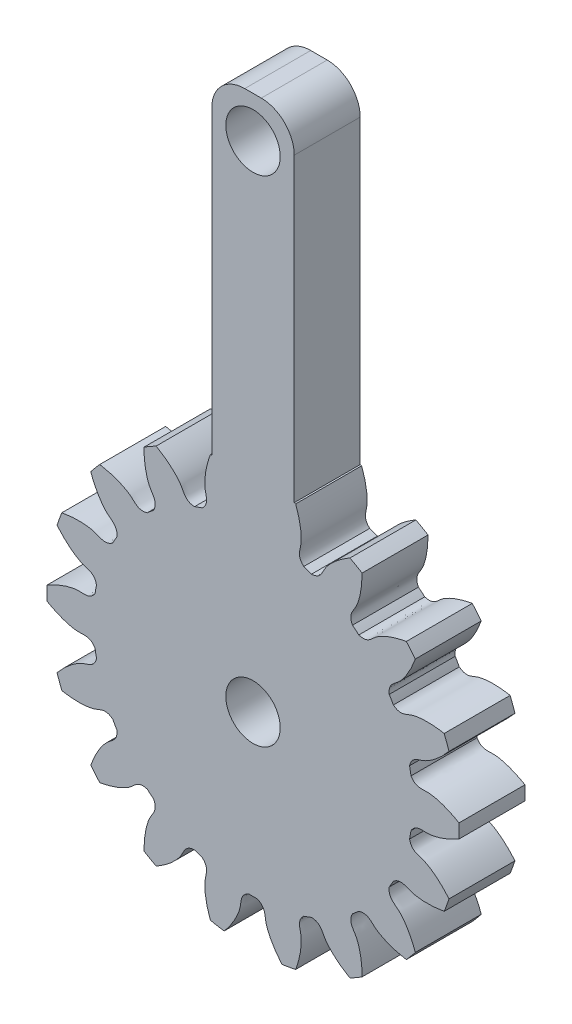
SolidWorks part; units mm, degrees
ref_plane "前视基准面" through (0, 0, 0) normal (0, 0, 1) x (1, 0, 0)
ref_plane "上视基准面" through (0, 0, 0) normal (0, 1, 0) x (1, 0, 0)
ref_plane "右视基准面" through (0, 0, 0) normal (1, 0, 0) x (0, 0, -1)
sketch "草图1" plane through (0, 0, 0) normal (0, 0, 1) x (1, 0, 0)
  circle A0 centre (0, 0) radius 12.5
extrude "凸台-拉伸1" add sketch "草图1" along normal blind 4
ref_axis "基准轴1" through (0, 0, -0.15) along (0, 0, 1)
sketch "草图2" plane through (0, 0, 0) normal (0, 0, 1) x (1, 0, 0)
  line L0 (0, 0) -> (0, 12.5) construction
  circle A0 centre (0, 0) radius 12.5 construction
  arc A1 (0.2493, 9.6843) -> (-0.2493, 9.6843) centre (0, 0) ccw
  arc A2 (3.8732, 14.1333) -> (-3.8732, 14.1333) centre (0, 0) ccw
  spline S0 degree 3 poles (0.2493, 9.6843) (0.7689, 9.8984) (0.7035, 10.2984) (0.7898, 10.6782) (0.7984, 10.7131) (0.8089, 10.7519) (0.8213, 10.7946) (0.8358, 10.841) (0.8526, 10.8911) (0.8718, 10.9449) (0.8935, 11.0022) (0.918, 11.063) (0.9453, 11.1272) (0.9757, 11.1947) (1.0092, 11.2654) (1.046, 11.3392) (1.0863, 11.416) (1.1301, 11.4956) (1.1776, 11.5781) (1.2289, 11.6632) (1.2842, 11.7508) (1.3435, 11.8408) (1.407, 11.9332) (1.4749, 12.0276) (1.5471, 12.1241) (1.6238, 12.2225) (1.7052, 12.3225) (1.7913, 12.4242) (1.8822, 12.5273) (1.978, 12.6316) (2.0788, 12.7371) (2.1846, 12.8436) (2.2956, 12.9508) (2.4118, 13.0587) (2.5334, 13.1671) (2.6602, 13.2757) (2.7925, 13.3845) (2.9303, 13.4932) (3.0735, 13.6017) (3.2224, 13.7099) (3.3768, 13.8174) (3.5926, 13.9613) (3.7594, 14.0654) (3.8732, 14.1333) knots 0 0 0 0 0.187592 0.192996 0.199121 0.205966 0.213531 0.221818 0.230824 0.240552 0.250999 0.262168 0.274057 0.286666 0.299996 0.314047 0.328818 0.344309 0.360521 0.377454 0.395107 0.413481 0.432575 0.45239 0.472926 0.494181 0.516158 0.538855 0.562272 0.58641 0.611269 0.636848 0.663148 0.690168 0.717909 0.74637 0.775552 0.805454 0.836077 0.867421 0.899485 0.932269 1 1 1 1
  spline S1 degree 3 poles (-0.2493, 9.6843) (-0.7689, 9.8984) (-0.7035, 10.2984) (-0.7898, 10.6782) (-0.7984, 10.7131) (-0.8089, 10.7519) (-0.8213, 10.7946) (-0.8358, 10.841) (-0.8526, 10.8911) (-0.8718, 10.9449) (-0.8935, 11.0022) (-0.918, 11.063) (-0.9453, 11.1272) (-0.9757, 11.1947) (-1.0092, 11.2654) (-1.046, 11.3392) (-1.0863, 11.416) (-1.1301, 11.4956) (-1.1776, 11.5781) (-1.2289, 11.6632) (-1.2842, 11.7508) (-1.3435, 11.8408) (-1.407, 11.9332) (-1.4749, 12.0276) (-1.5471, 12.1241) (-1.6238, 12.2225) (-1.7052, 12.3225) (-1.7913, 12.4242) (-1.8822, 12.5273) (-1.978, 12.6316) (-2.0788, 12.7371) (-2.1846, 12.8436) (-2.2956, 12.9508) (-2.4118, 13.0587) (-2.5334, 13.1671) (-2.6602, 13.2757) (-2.7925, 13.3845) (-2.9303, 13.4932) (-3.0735, 13.6017) (-3.2224, 13.7099) (-3.3768, 13.8174) (-3.5926, 13.9613) (-3.7594, 14.0654) (-3.8732, 14.1333) knots 0 0 0 0 0.187592 0.192996 0.199121 0.205966 0.213531 0.221818 0.230824 0.240552 0.250999 0.262168 0.274057 0.286666 0.299996 0.314047 0.328818 0.344309 0.360521 0.377454 0.395107 0.413481 0.432575 0.45239 0.472926 0.494181 0.516158 0.538855 0.562272 0.58641 0.611269 0.636848 0.663148 0.690168 0.717909 0.74637 0.775552 0.805454 0.836077 0.867421 0.899485 0.932269 1 1 1 1
extrude "切除-拉伸1" cut sketch "草图2" along normal through all
pattern_circular "阵列(圆周)1" count 18 every 20 about axis through (0, 0, -0.15) along (0, 0, 1) of "切除-拉伸1"
sketch "草图3" plane through (0, 0, 0) normal (0, 0, 1) x (1, 0, 0)
  circle A0 centre (0, 0) radius 11.25 construction
  dimension "Dn" = 22.5
sketch "草图4" plane through (0, 0, 4) normal (0, 0, 1) x (1, 0, 0)
  circle A0 centre (0, 0) radius 1.65
  dimension "D1" = 3.3
extrude "切除-拉伸2" cut sketch "草图4" against normal blind 10
sketch "草图5" plane through (0, 0, 4) normal (0, 0, 1) x (1, 0, 0)
  line L1 (-2.5, 32.5) -> (2.5, 32.5)
  line L2 (-2.5, 32.5) -> (-2.5, 8.1858)
  line L3 (-2.5, 8.1858) -> (2.5, 8.1858)
  line L4 (2.5, 32.5) -> (2.5, 8.1858)
  line L5 (-2.5, 32.5) -> (2.5, 8.1858) construction
  line L6 (-2.5, 8.1858) -> (2.5, 32.5) construction
  circle A0 centre (0, 30) radius 1.65
  point P0 (0, 20.3429)
  dimension "D3" = 3.3
  dimension "D1" = 5
  dimension "D2" = 30
  dimension "D4" = 2.5
extrude "凸台-拉伸2" add sketch "草图5" against normal up to surface (4 mm away) up to face at (1.65, 0, 0)
fillet "圆角1" radius 2 2 edges at (-2.5, 32.5, 2) (2.5, 32.5, 2)
